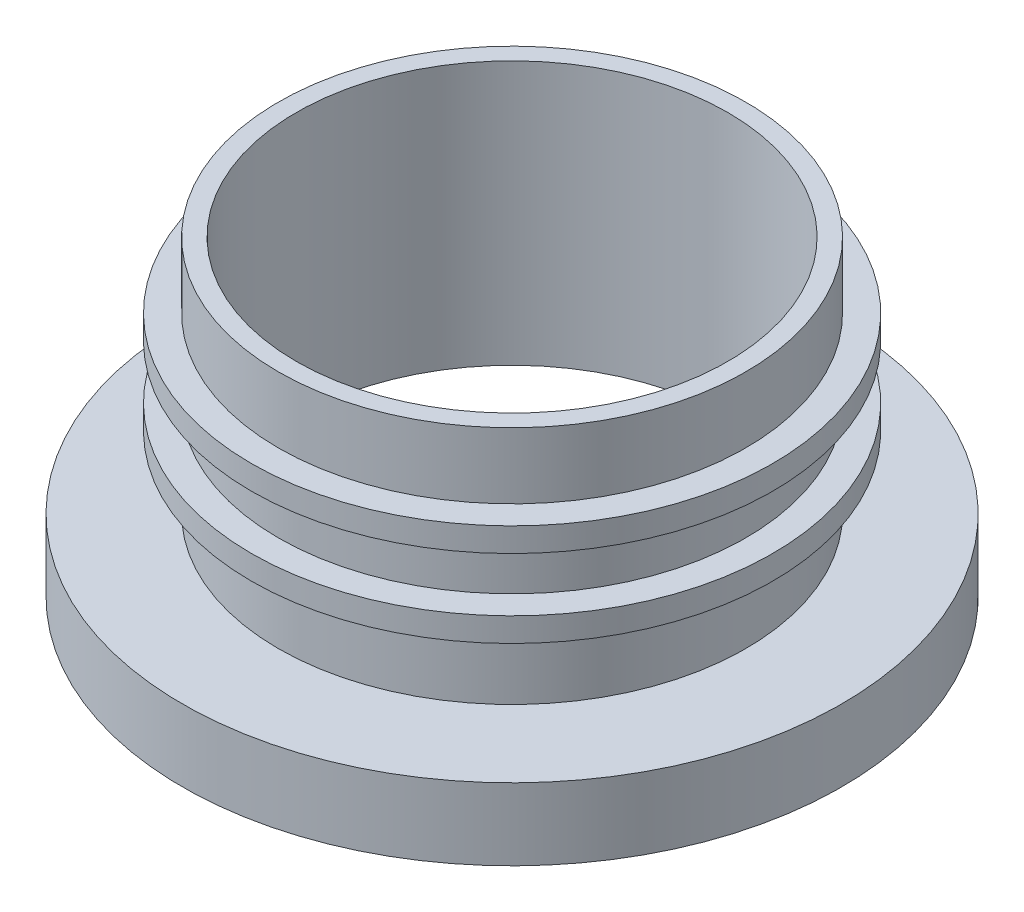
SolidWorks part; units mm, degrees
ref_plane "前基準面" through (0, 0, 0) normal (0, 0, 1) x (1, 0, 0)
ref_plane "上基準面" through (0, 0, 0) normal (0, 1, 0) x (1, 0, 0)
ref_plane "右基準面" through (0, 0, 0) normal (1, 0, 0) x (0, 0, -1)
sketch "草圖1" plane through (0, 0, 0) normal (0, 1, 0) x (1, 0, 0)
  circle A0 centre (0, 0) radius 19.5
  circle A1 centre (0, 0) radius 18
  dimension "D1" = 39
  dimension "D2" = 36
extrude "填料-伸長1" add sketch "草圖1" along normal blind 20
sketch "草圖3" plane through (0, 0, 0) normal (0, -1, 0) x (1, 0, 0)
  circle A0 centre (0, 0) radius 27.5
  dimension "D1" = 55
extrude "填料-伸長2" add sketch "草圖3" along normal blind 2
ref_plane "平面1" through (0, 8, 0) normal (0, 1, 0) x (1, 0, 0)
sketch "草圖4" plane through (0, 8, 0) normal (0, 1, 0) x (1, 0, 0)
  circle A0 centre (0, 0) radius 21.75
  dimension "D1" = 43.5
extrude "填料-伸長3" add sketch "草圖4" against normal blind 2
sketch "草圖6" plane through (0, 0, 0) normal (0, 1, 0) x (1, 0, 0)
  circle A0 centre (0, 0) radius 18
  dimension "D1" = 36
ref_plane "平面2" through (0, 11.5, 0) normal (0, 1, 0) x (1, 0, 0)
sketch "草圖8" plane through (0, 11.5, 0) normal (0, 1, 0) x (1, 0, 0)
  circle A0 centre (0, 0) radius 21.75
extrude "填料-伸長4" add sketch "草圖8" along normal blind 2 from offset 1
extrude "除料-伸長1" cut sketch "草圖6" along normal blind 35
ref_plane "平面3" through (0, -2, 0) normal (0, -1, 0) x (-1, 0, 0)
sketch "草圖13" plane through (0, -2, 0) normal (0, -1, 0) x (1, 0, 0)
  circle A0 centre (0, 0) radius 18
  circle A1 centre (0, 0) radius 21.5
  circle A2 centre (0, 0) radius 25
  circle A3 centre (0, 0) radius 27.5
  circle M1 centre (0, 0) radius 27.5
  dimension "D1" = 36
  dimension "D2" = 43
  dimension "D3" = 50
  dimension "D4" = 55
extrude "填料-伸長6" add sketch "草圖13" along normal blind 4 contours A2 M1 region at (-26.7222, -2, 0)
extrude "除料-伸長2" cut sketch "草圖13<4>" against normal blind 23.5 contours A0 region at (0, -2, 0)
sketch "草圖13<4>" plane through (0, -2, 0) normal (0, -1, 0) x (1, 0, 0) same geometry as "草圖13"
